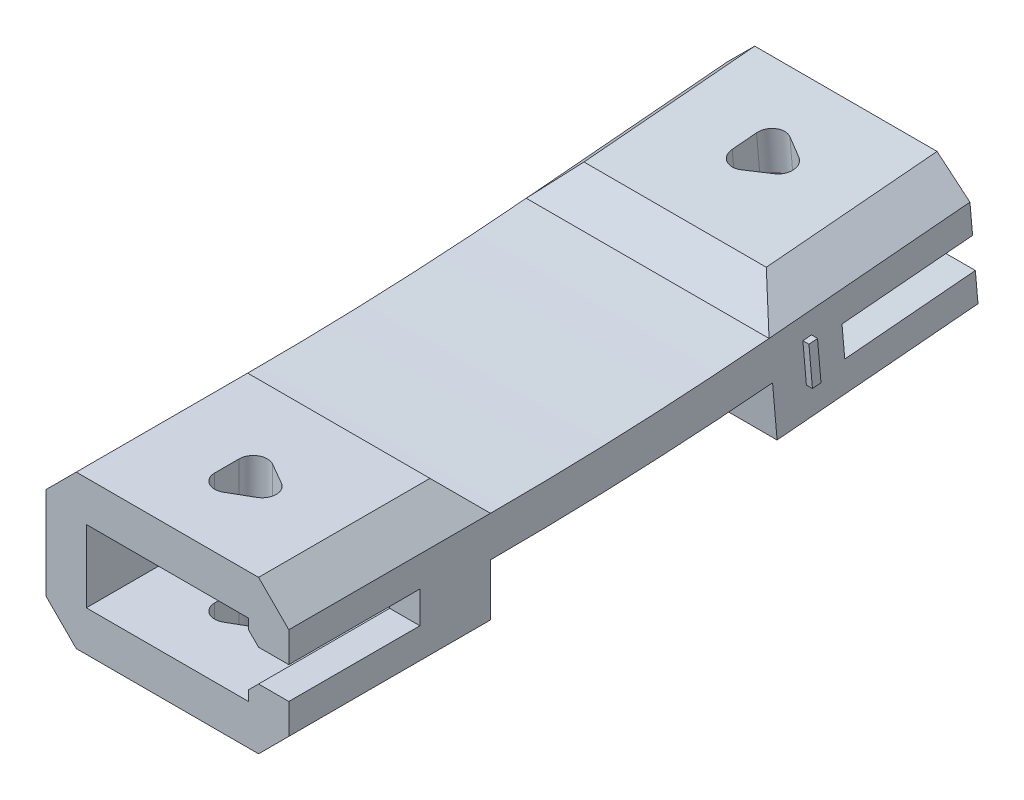
SolidWorks part; units mm, degrees
ref_plane "Front Plane" through (0, 0, 0) normal (0, 0, 1) x (1, 0, 0)
ref_plane "Top Plane" through (0, 0, 0) normal (0, 1, 0) x (1, 0, 0)
ref_plane "Right Plane" through (0, 0, 0) normal (1, 0, 0) x (0, 0, -1)
other "Configuration Table"
sketch "Sketch1" plane through (0, 0, 0) normal (0, 0, 1) x (1, 0, 0)
  line L1 (4.02, -1.79) -> (-4.02, -1.79)
  line L2 (4.02, -1.79) -> (4.02, 1.79)
  line L3 (4.02, 1.79) -> (-4.02, 1.79)
  line L4 (-4.02, -1.79) -> (-4.02, 1.79)
  line L5 (0, 1.79) -> (0, -1.79) construction
  line L6 (4.02, 0) -> (-4.02, 0) construction
  line L7 (-6.02, 3.79) -> (6.02, 3.79)
  line L8 (-6.02, 3.79) -> (-6.02, -3.79)
  line L9 (-6.02, -3.79) -> (6.02, -3.79)
  line L10 (6.02, 3.79) -> (6.02, -3.79)
  line L11 (0, -3.79) -> (0, 3.79) construction
  line L12 (-6.02, 0) -> (6.02, 0) construction
  point P0 (0, 0)
  point P4 (0, 0)
  dimension "D1" = 3.58
  dimension "D2" = 8.04
  dimension "D3" = 2
  dimension "D4" = 2
extrude "Boss-Extrude1" add sketch "Sketch1" along normal blind 8
extrude "Boss-Extrude2" add sketch "Sketch1<2>" against normal blind 2 contours L4 L1 L2 L3 | L10 L7 L8 L9 L1 L4 L3 L2 region at (0, 0, 0) region at (0, 3.6477, 0)
sketch "Sketch1<2>" plane through (0, 0, 0) normal (0, 0, 1) x (1, 0, 0) same geometry as "Sketch1"
sketch "Sketch3" plane through (6.02, 9.81, 0) normal (1, 0, 0) x (0, -1, 0)
  line L0 (13.6, 2) -> (9.52, 2)
  line L2 (8.9093, 15.9867) -> (12.9738, 16.3423)
  line L3 (13.6, -8) -> (13.6, 2) construction
  arc A1 (9.52, 2) -> (8.9093, 15.9867) centre (-150.9591, 2) ccw
  arc A3 (12.9738, 16.3423) -> (13.6, 2) centre (-150.9591, 2) cw construction
  dimension "D1" = 4.08
  dimension "D4" = 5
  dimension "D2" = 14
extrude "Extrude-Thin1" add sketch "Sketch3" along normal up to surface (-12.04 mm away) thin contours L0 A1 L2 up to face at (-6.02, 0, 3) thin type one direction reverse wall 2
sketch "Sketch5" plane through (0, -2.3561, -16.2716) normal (0, 0.0872, -0.9962) x (-1, 0, 0)
  line L1 (4.02, 1.1892) -> (-4.02, 1.1892)
  line L2 (4.02, 1.1892) -> (4.02, 4.7692)
  line L3 (4.02, 4.7692) -> (-4.02, 4.7692)
  line L4 (-4.02, 1.1892) -> (-4.02, 4.7692)
  line L5 (0, 4.7692) -> (0, 1.1892) construction
  line L6 (4.02, 2.9792) -> (-4.02, 2.9792) construction
  line L7 (-6.02, 6.7692) -> (6.02, 6.7692)
  line L8 (-6.02, 6.7692) -> (-6.02, -0.8108)
  line L9 (-6.02, -0.8108) -> (6.02, -0.8108)
  line L10 (6.02, 6.7692) -> (6.02, -0.8108)
  line L11 (0, -0.8108) -> (0, 6.7692) construction
  line L12 (-6.02, 2.9792) -> (6.02, 2.9792) construction
  line L13 (6.02, -0.8108) -> (-6.02, -0.8108) construction
  point P0 (0, 2.9792)
  point P4 (0, 2.9792)
  line M23 (6.02, -0.8108) -> (-6.02, -0.8108)
  line M29 (-6.02, 3.2692) -> (6.02, 3.2692)
  dimension "D1" = 3.58
  dimension "D2" = 8.04
  dimension "D3" = 2
  dimension "D4" = 2
extrude "Boss-Extrude4" add sketch "Sketch5" along normal blind 10 contours M29 M23 | L7 L10 L2 L3 L4 L8 M29 region at (0, -1.6457, -16.2095) region at (0, 3.0434, -15.7992)
extrude "Boss-Extrude5" add sketch "Sketch5<4>" along normal blind 2 contours L8 L7 L10 L9
sketch "Sketch5<4>" plane through (0, -2.3561, -16.2716) normal (0, 0.0872, -0.9962) x (-1, 0, 0) same geometry as "Sketch5"
chamfer "Chamfer1" distance 1.5 angle 45 12 edges at (-6.02, 4.8231, -20.6626) (6.02, 4.8231, -20.6626) (6.02, 3.79, 3) (6.02, -3.79, 3) (-6.02, -3.79, 3) (-6.02, 3.79, 3) (0, 3.79, -2) (0, -3.1638, -16.3423) (6.02, -2.728, -21.3232) (-6.02, -2.728, -21.3232) (0, -3.79, -2) (0, 4.3874, -15.6816)
sketch "Sketch6" plane through (0, 3.79, 0) normal (0, 1, 0) x (1, 0, 0)
  line L0 (0, 2) -> (0, -8) construction
  line L4 (1.05, -3.3938) -> (0, -2.7876)
  line L5 (-1.05, -3.3938) -> (-1.05, -4.6062)
  line L6 (0, -5.2124) -> (1.05, -4.6062)
  line L7 (-6.02, 2) -> (6.02, 2) construction
  line L8 (4.52, -8) -> (-4.52, -8) construction
  line L9 (4.02, 0) -> (-4.02, 0) construction
  circle A0 centre (0, -4) radius 1.05 construction
  arc A1 (-1.05, -4.6062) -> (0, -5.2124) centre (-0.35, -4.6062) ccw
  arc A2 (0, -2.7876) -> (-1.05, -3.3938) centre (-0.35, -3.3938) ccw
  arc A3 (1.05, -3.3938) -> (1.05, -4.6062) centre (0.7, -4) cw
  point P15 (-1.05, -5.8187)
  point P18 (-1.05, -2.1813)
  dimension "D3" = 0.7
  dimension "D1" = 2.1
  dimension "D2" = 4
sketch "Sketch7" plane through (0, 2.9925, 0.2618) normal (0, 0.9962, 0.0872) x (1, 0, 0)
  line L0 (0, 26.0043) -> (0, 16.0043) construction
  line L4 (1.05, 22.6106) -> (0, 23.2168)
  line L5 (-1.05, 22.6106) -> (-1.05, 21.3981)
  line L6 (0, 20.7919) -> (1.05, 21.3981)
  line L7 (6.02, 16.0043) -> (-6.02, 16.0043) construction
  line L8 (4.52, 26.0043) -> (-4.52, 26.0043) construction
  line L9 (-4.02, 18.0043) -> (4.02, 18.0043) construction
  circle A0 centre (0, 22.0043) radius 1.05 construction
  arc A1 (-1.05, 21.3981) -> (0, 20.7919) centre (-0.35, 21.3981) ccw
  arc A2 (1.05, 22.6106) -> (1.05, 21.3981) centre (0.7, 22.0043) cw
  arc A3 (0, 23.2168) -> (-1.05, 22.6106) centre (-0.35, 22.6106) ccw
  dimension "D1" = 2.1
  dimension "D3" = 0.7
  dimension "D2" = 4
extrude "Cut-Extrude1" cut sketch "Sketch6" against normal through all both and the other way through all
extrude "Cut-Extrude2" cut sketch "Sketch7" against normal through all both and the other way through all
sketch "Sketch8" plane through (0, 2.2664, -25.9054) normal (0, 0.0872, -0.9962) x (-1, 0, 0)
  line L1 (-8.02, 0.0039) -> (-4.02, 0.0039)
  line L2 (-8.02, 0.0039) -> (-8.02, -1.5761)
  line L3 (-8.02, -1.5761) -> (-4.02, -1.5761)
  line L4 (-4.02, 0.0039) -> (-4.02, -1.5761)
  line L5 (-6.02, -1.5761) -> (-6.02, 0.0039) construction
  line L6 (-8.02, -0.7861) -> (-4.02, -0.7861) construction
  line L8 (-6.02, -3.0761) -> (-6.02, 1.5039) construction
  line L9 (-4.02, -2.5761) -> (-4.02, 1.0039) construction
  line L10 (4.02, -2.5761) -> (-4.02, -2.5761) construction
  point P0 (-6.02, -0.7861)
  dimension "D1" = 1.58
  dimension "D2" = 4
  dimension "D3" = 1
extrude "Cut-Extrude3" cut sketch "Sketch8" against normal offset from surface (6.5 mm away) 1.5 up to face at (0, 0.7861, -18.0043)
sketch "Sketch9" plane through (0, 0, 8) normal (0, 0, 1) x (1, 0, 0)
  line L1 (8.02, 0.79) -> (4.02, 0.79)
  line L2 (8.02, 0.79) -> (8.02, -0.79)
  line L3 (8.02, -0.79) -> (4.02, -0.79)
  line L4 (4.02, 0.79) -> (4.02, -0.79)
  line L5 (6.02, -0.79) -> (6.02, 0.79) construction
  line L6 (8.02, 0) -> (4.02, 0) construction
  line L8 (6.02, -2.29) -> (6.02, 2.29) construction
  line L9 (4.02, -1.79) -> (4.02, 1.79) construction
  line L10 (-4.02, -1.79) -> (4.02, -1.79) construction
  point P0 (6.02, 0)
  dimension "D1" = 1.58
  dimension "D2" = 4
  dimension "D3" = 1
extrude "Cut-Extrude4" cut sketch "Sketch9" against normal offset from surface (6.5 mm away) 1.5 up to face at (0, 0, 0)
chamfer "Chamfer2" distance 0.5 angle 45 6 edges at (4.02, 1.9871, -22.6674) (4.02, 0.9168, -19.4986) (4.02, 0.4131, -22.8051) (4.02, 0.79, 4.75) (4.02, 0, 1.5) (4.02, -0.79, 4.75)
sketch "Sketch10" [suppressed] plane through (6.02, 0, 0) normal (1, 0, 0) x (0, 0, -1)
  line L0 (22.5646, 0.2607) -> (19.0779, -0.0444) construction
  line L2 (18.9838, 1.0315) -> (19.2087, -1.5387) construction
  line L3 (22.5646, 0.2607) -> (22.4269, 1.8347) construction
  line L4 (29.0399, 0.8272) -> (22.5646, 0.2607) construction
  text T0 "<b>III</b>" font "@Microsoft YaHei" height 2
extrude "Boss-Extrude6" [suppressed] add sketch "Sketch10" along normal blind 0.3
sketch "Sketch11" [suppressed] plane through (6.02, 0, 0) normal (1, 0, 0) x (0, 0, -1)
  line L0 (21.5656, 0.2171) -> (18.0789, -0.088) construction
  line L1 (17.9848, 0.9879) -> (18.2096, -1.5823) construction
  line L2 (28.0408, 0.7836) -> (21.5656, 0.2171) construction
  text T0 "<b>II</b>\r\n" font "@Microsoft YaHei" height 2
extrude "Boss-Extrude7" [suppressed] add sketch "Sketch11" along normal blind 0.3
sketch "Sketch12" plane through (6.02, 0, 0) normal (1, 0, 0) x (0, 0, -1)
  line L0 (19.5675, 0.1298) -> (16.0808, -0.1752) construction
  line L1 (15.9867, 0.9007) -> (16.2115, -1.6695) construction
  line L2 (26.0428, 0.6963) -> (19.5675, 0.1298) construction
  text T0 "<b>I</b>\r\n" font "@Microsoft YaHei" height 2
extrude "Boss-Extrude8" add sketch "Sketch12" along normal blind 0.3
equation "\"LF\" = 0.04mm"
equation "\"TF\" = 0.02mm"
equation "\"AngLF\"= 0.5deg"
equation "\"AngTF\"= 0.3deg"
equation "\"D2@Sketch1\"=8+2*\"TF\""
equation "\"D1@Sketch1\"=3.5+2*\"LF\""
